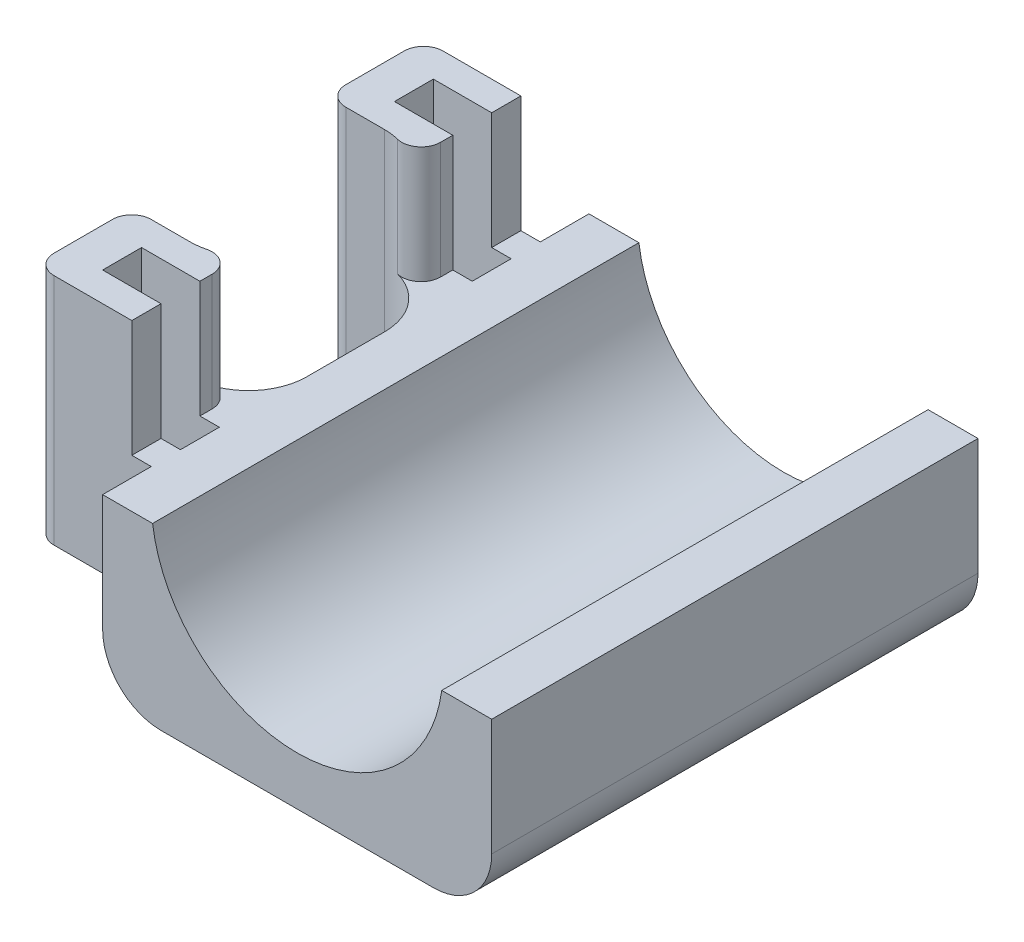
SolidWorks part; units mm, degrees
ref_plane "Plano frontal" through (0, 0, 0) normal (0, 0, 1) x (1, 0, 0)
ref_plane "Plano superior" through (0, 0, 0) normal (0, 1, 0) x (1, 0, 0)
ref_plane "Plano direito" through (0, 0, 0) normal (1, 0, 0) x (0, 0, -1)
sketch "Esboço1" plane through (0, 0, 0) normal (0, 1, 0) x (1, 0, 0)
  line L1 (-10, 12.5) -> (10, 12.5)
  line L2 (-10, 12.5) -> (-10, -12.5)
  line L3 (-10, -12.5) -> (10, -12.5)
  line L4 (10, 12.5) -> (10, -12.5)
  line L5 (-10, 12.5) -> (10, -12.5) construction
  line L6 (-10, -12.5) -> (10, 12.5) construction
  point P0 (0, 0)
  dimension "D1" = 20
  dimension "D2" = 25
extrude "Ressalto-extrusão1" add sketch "Esboço1" along normal blind 9
sketch "Esboço2" plane through (0, 0, 12.5) normal (0, 0, 1) x (1, 0, 0)
  line L0 (-10, 9) -> (10, 9) construction
  circle A0 centre (0, 10) radius 7.5
  point P2 (0, 0)
  dimension "D2" = 15
  dimension "D1" = 1
extrude "Corte-extrusão1" cut sketch "Esboço2" against normal through all
fillet "Filete1" radius 3 2 edges at (10, 0, 0) (-10, 0, 0)
sketch "Esboço3" plane through (0, 9, 0) normal (0, 1, 0) x (1, 0, 0)
  line L0 (-16, 10) -> (-10, 5) construction
  line L5 (-10, 12.5) -> (-10, -12.5) construction
  line L10 (-9.5, -5) -> (-16.5, -10) construction
  line L15 (-16, 10) -> (-10, 10)
  line L16 (-16, 10) -> (-16, 5)
  line L17 (-16, 5) -> (-10, 5)
  line L18 (-10, 10) -> (-10, 8.5)
  line L19 (-13, 7.5) -> (-13, -7.5) construction
  line L20 (-10, 6.5) -> (-10, 5)
  line L21 (-14, 8.5) -> (-10, 8.5)
  line L22 (-14, 8.5) -> (-14, 6.5)
  line L23 (-14, 6.5) -> (-10, 6.5)
  line L25 (0, 0) -> (-10, 0) construction
  line L26 (-14, -6.5) -> (-10, -6.5)
  line L27 (-14, -8.5) -> (-14, -6.5)
  line L28 (-14, -8.5) -> (-10, -8.5)
  line L29 (-10, -6.5) -> (-10, -5)
  line L30 (-10, -10) -> (-10, -8.5)
  line L31 (-16, -5) -> (-10, -5)
  line L32 (-16, -10) -> (-16, -5)
  line L33 (-16, -10) -> (-10, -10)
  point P14 (-13, 0)
  point P22 (-14, 7.5)
  dimension "D1" = 15
  dimension "D2" = 6
  dimension "D3" = 5
  dimension "D4" = 4
  dimension "D5" = 2
extrude "Ressalto-extrusão2" add sketch "Esboço3" against normal blind 6
sketch "Esboço4" plane through (0, 9, 0) normal (0, 1, 0) x (1, 0, 0)
  line L0 (-16, -10) -> (-16, -5)
  line L1 (-16, -5) -> (-11, -5)
  line L2 (-10, -5) -> (-16, -5) construction
  line L3 (-11, -5) -> (-11, -6.5)
  line L4 (-14, -6.5) -> (-10, -6.5) construction
  line L5 (-11, -6.5) -> (-14, -6.5)
  line L6 (-14, -6.5) -> (-14, -8.5)
  line L7 (-14, -8.5) -> (-11, -8.5)
  line L8 (-10, -8.5) -> (-14, -8.5) construction
  line L9 (-11, -8.5) -> (-11, -10)
  line L10 (-16, -10) -> (-10, -10) construction
  line L11 (-11, -10) -> (-16, -10)
  line L12 (-10, 5) -> (-10, -5) construction
  line L13 (0, 0) -> (-10, 0) construction
  line L14 (-11, 10) -> (-16, 10)
  line L15 (-11, 8.5) -> (-11, 10)
  line L16 (-14, 8.5) -> (-11, 8.5)
  line L17 (-14, 6.5) -> (-14, 8.5)
  line L18 (-11, 6.5) -> (-14, 6.5)
  line L19 (-11, 5) -> (-11, 6.5)
  line L20 (-16, 5) -> (-11, 5)
  line L21 (-16, 10) -> (-16, 5)
  dimension "D1" = 1
extrude "Ressalto-extrusão3" add sketch "Esboço4" along normal blind 6
fillet "Filete3" radius 1 4 edges at (-16, 9, -10) (-16, 9, -5) (-16, 9, 5) (-16, 9, 10)
fillet "Filete5" radius 3 2 edges at (-10, 6, -5) (-10, 6, 5)
fillet "Filete6" radius 1 2 edges at (-11, 12, -4.2361) (-11, 12, 4.2361)
